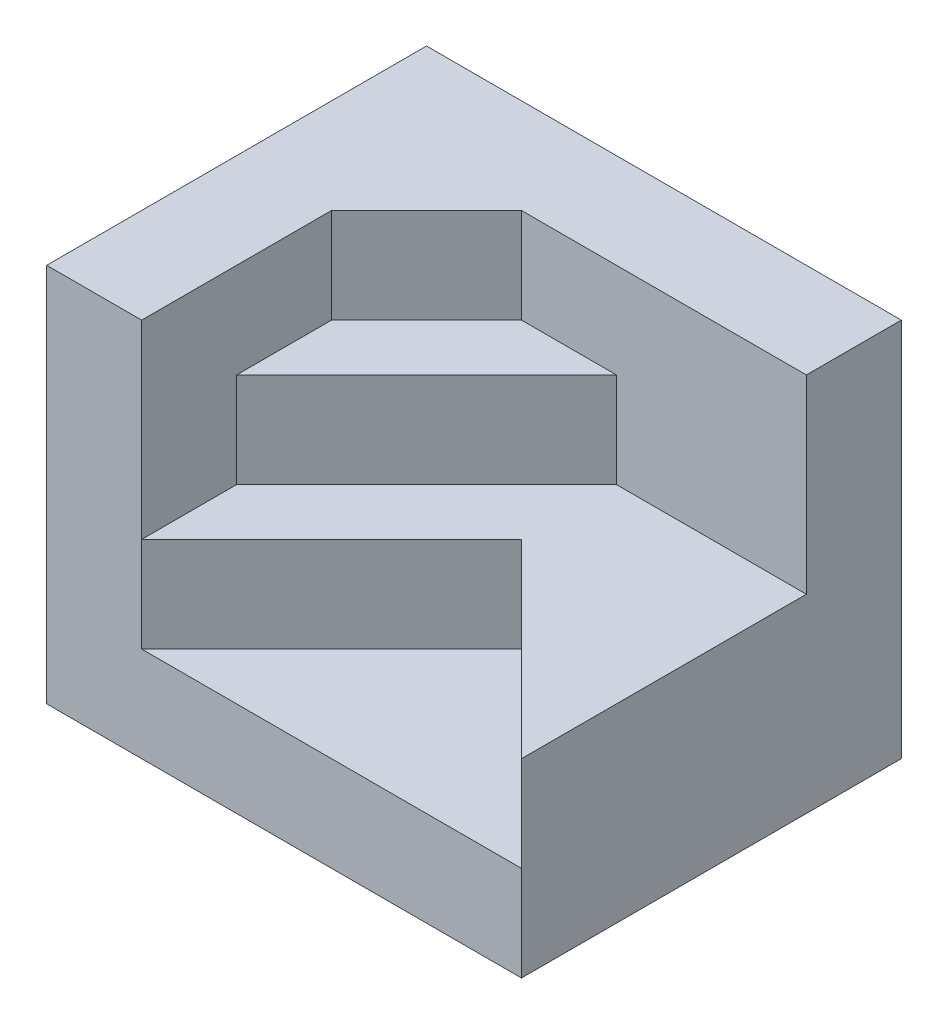
SolidWorks part; units mm, degrees
ref_plane "Front Plane" through (0, 0, 0) normal (0, 0, 1) x (1, 0, 0)
ref_plane "Top Plane" through (0, 0, 0) normal (0, 1, 0) x (1, 0, 0)
ref_plane "Right Plane" through (0, 0, 0) normal (1, 0, 0) x (0, 0, -1)
sketch "Sketch1" plane through (0, 0, 0) normal (0, 1, 0) x (1, 0, 0)
  line L0 (0, 0) -> (0, 40)
  line L1 (0, 40) -> (50, 40)
  line L2 (50, 40) -> (50, 0)
  line L3 (50, 0) -> (0, 0)
  line L4 (10, 0) -> (10, 20)
  line L5 (10, 20) -> (20, 30)
  line L6 (20, 30) -> (50, 30)
  line L7 (30, 30) -> (10, 10)
  line L8 (10, 0) -> (30, 20)
  line L9 (30, 20) -> (50, 0)
  dimension "D1" = 40
  dimension "D2" = 50
  dimension "D3" = 40
  dimension "D4" = 30
  dimension "D5" = 10
  dimension "D6" = 20
  dimension "D7" = 30
  dimension "D8" = 45
  dimension "D9" = 20
  dimension "D10" = 45
extrude "Boss-Extrude1" add sketch "Sketch1" along normal blind 10 contours L9 L8 L3 region at (30, 0, -6.6667)
extrude "Boss-Extrude2" add sketch "Sketch1<3>" along normal blind 20 contours L8 L9 L2 L6 L7 L4 region at (34.4444, 0, -17.7778)
sketch "Sketch1<3>" plane through (0, 0, 0) normal (0, 1, 0) x (1, 0, 0) same geometry as "Sketch1"
extrude "Boss-Extrude3" add sketch "Sketch1<4>" along normal blind 30 contours L7 L6 L5 L4 region at (17.7778, 0, -22.2222)
sketch "Sketch1<4>" plane through (0, 0, 0) normal (0, 1, 0) x (1, 0, 0) same geometry as "Sketch1"
extrude "Boss-Extrude4" add sketch "Sketch1<5>" along normal blind 40 contours L5 L6 L2 L1 L0 L3 L4 region at (17.2549, 0, -27.451)
sketch "Sketch1<5>" plane through (0, 0, 0) normal (0, 1, 0) x (1, 0, 0) same geometry as "Sketch1"
